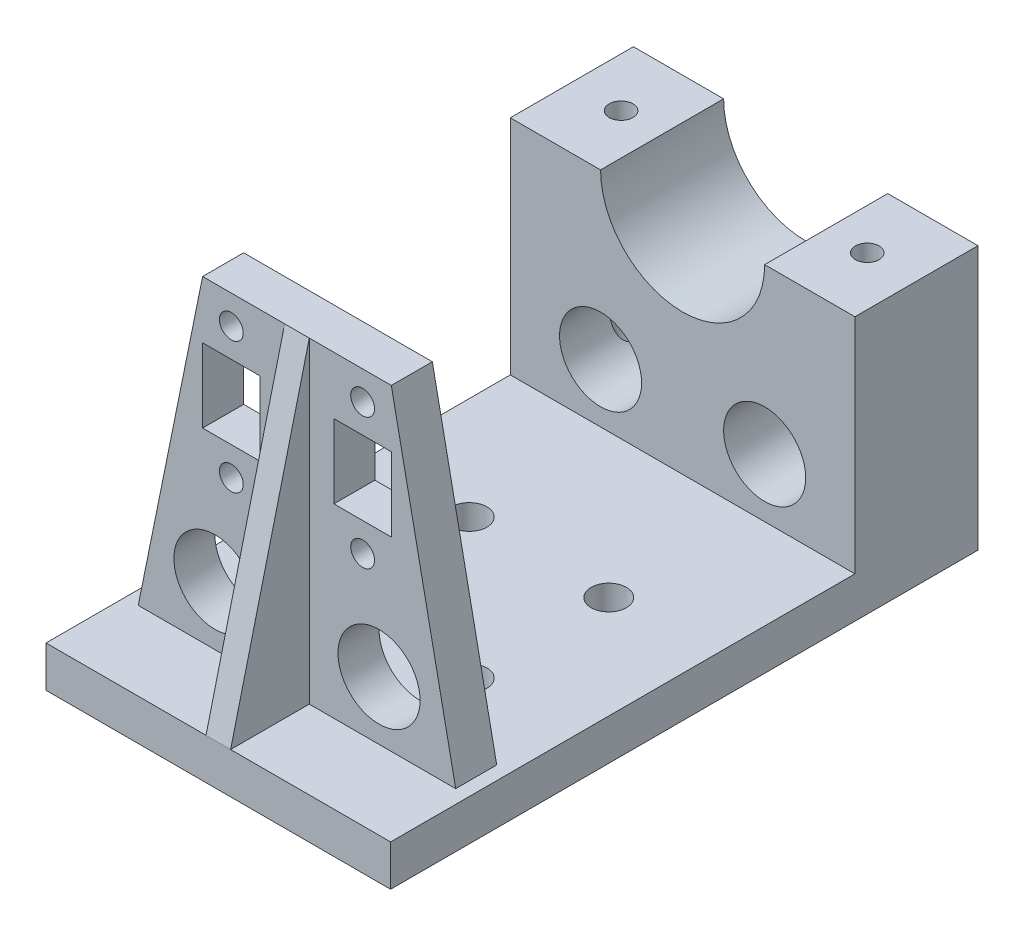
SolidWorks part; units mm, degrees
material "ABS"
ref_plane "Front Plane" through (0, 0, 0) normal (0, 0, 1) x (1, 0, 0)
ref_plane "Top Plane" through (0, 0, 0) normal (0, 1, 0) x (1, 0, 0)
ref_plane "Right Plane" through (0, 0, 0) normal (1, 0, 0) x (0, 0, -1)
sketch "Mouting Mount Sketch" plane through (0, 0, 0) normal (0, 0, 1) x (1, 0, 0)
  line L1 (25, -55) -> (-25, -55)
  line L2 (25, -55) -> (25, 0)
  line L3 (25, 0) -> (-25, 0)
  line L4 (-25, -55) -> (-25, 0)
  line L5 (25, -55) -> (-25, 0) construction
  line L6 (25, 0) -> (-25, -55) construction
  circle A0 centre (0, 0) radius 10
  point P3 (0, -27.5)
  dimension "D1" = 20
  dimension "D2" = 50
  dimension "D3" = 55
extrude "Motor Mount Solid" add sketch "Mouting Mount Sketch" along normal mid plane 15 contours A0 L3 L4 L1 L2 region at (0, -28.9088, 0)
sketch "Encoder Distance Sketch" plane through (0, -55, 0) normal (0, -1, 0) x (1, 0, 0)
  line L0 (25, 7.5) -> (25, -7.5) construction
  line L1 (-25, 7.5) -> (25, 7.5)
  line L2 (-25, 7.5) -> (-25, 49.5)
  line L3 (-25, 49.5) -> (25, 49.5)
  line L4 (25, 7.5) -> (25, 49.5)
  line L5 (-25, -7.5) -> (25, -7.5) construction
  line L6 (-25, -7.5) -> (-25, 54.5) construction
  line L7 (-25, 54.5) -> (25, 54.5) construction
  line L8 (25, -7.5) -> (25, 54.5) construction
  line M9 (-25, -7.5) -> (25, -7.5)
  line M10 (25, -7.5) -> (25, 7.5)
  line M11 (25, 7.5) -> (-25, 7.5)
  line M12 (-25, 7.5) -> (-25, -7.5)
  dimension "D1" = 42
  dimension "D2" = 5
extrude "Encoder Distance Solid" add sketch "Encoder Distance Sketch" along normal blind 5 contours M12 M9 M10 M11 | L4 L3 L2 M11 | L3 L8 L7 L6 region at (0, -55, 28.5) region at (0, -55, 0)
sketch "Encoder Mount Sketch" plane through (0, 0, 49.5) normal (0, 0, 1) x (1, 0, 0)
  line L0 (-25, -60) -> (-25, -55)
  line L1 (-8, -8) -> (8, -8) construction
  line L2 (-8, -8) -> (-8, 8) construction
  line L3 (-8, 8) -> (8, 8) construction
  line L4 (8, -8) -> (8, 8) construction
  line L5 (-8, -8) -> (8, 8) construction
  line L6 (-8, 8) -> (8, -8) construction
  line L7 (-11.5, -11.5) -> (11.5, -11.5) construction
  line L8 (-11.5, -11.5) -> (-11.5, 11.5) construction
  line L9 (-11.5, 11.5) -> (11.5, 11.5)
  line L10 (11.5, -11.5) -> (11.5, 11.5) construction
  line L11 (-11.5, -11.5) -> (11.5, 11.5) construction
  line L12 (-11.5, 11.5) -> (11.5, -11.5) construction
  line L13 (-11.5, 4.5) -> (-4.5, 4.5)
  line L14 (-11.5, 4.5) -> (-11.5, -4.5)
  line L15 (-11.5, -4.5) -> (-4.5, -4.5)
  line L16 (-4.5, 4.5) -> (-4.5, -4.5)
  line L17 (-11.5, 4.5) -> (-4.5, -4.5) construction
  line L18 (-11.5, -4.5) -> (-4.5, 4.5) construction
  line L19 (4.5, 4.5) -> (11.5, 4.5)
  line L20 (4.5, 4.5) -> (4.5, -4.5)
  line L21 (4.5, -4.5) -> (11.5, -4.5)
  line L22 (11.5, 4.5) -> (11.5, -4.5)
  line L23 (4.5, 4.5) -> (11.5, -4.5) construction
  line L24 (4.5, -4.5) -> (11.5, 4.5) construction
  line L25 (-25, -55) -> (-11.5, 11.5)
  line L26 (-25, -60) -> (25, -60)
  line L27 (25, -60) -> (25, -55)
  line L28 (25, -55) -> (11.5, 11.5)
  circle A0 centre (-8, 8) radius 1.45
  circle A1 centre (8, 8) radius 1.45
  circle A2 centre (-8, -8) radius 1.45
  circle A3 centre (8, -8) radius 1.45
  circle A4 centre (8, 8) radius 3.5 construction
  circle A5 centre (-8, 8) radius 3.5 construction
  circle A6 centre (-8, -8) radius 3.5 construction
  circle A7 centre (8, -8) radius 3.5 construction
  point P0 (0, 0)
  point P14 (0, 0)
  point P19 (-8, 0)
  point P24 (8, 0)
  dimension "D2" = 2.9
  dimension "D3" = 7
  dimension "D1" = 16
extrude "Encoder Mount Solid" add sketch "Encoder Mount Sketch" along normal blind 5
sketch "Motor Clamp Mounting Holes Sketch" plane through (0, 0, 0) normal (0, 1, 0) x (1, 0, 0)
  line L0 (-15, 0) -> (15, 0) construction
  circle A0 centre (-15, 0) radius 1.45
  circle A1 centre (15, 0) radius 1.45
  point P4 (0, 0)
  dimension "D2" = 2.9
  dimension "D1" = 30
extrude "Motor Clamp Mounting Holes Cut" cut sketch "Motor Clamp Mounting Holes Sketch" against normal through all both and the other way through all
sketch "Gusset Plate Sketch" plane through (0, 0, 54.5) normal (0, 0, 1) x (1, 0, 0)
  line L1 (-25, -55) -> (25, -55)
  line L2 (-25, -55) -> (-25, -60)
  line L3 (-25, -60) -> (25, -60)
  line L4 (25, -55) -> (25, -60)
extrude "Gusset Plate Solid" add sketch "Gusset Plate Sketch" along normal blind 16.5
sketch "Gusset Sketch" plane through (0, 0, 0) normal (1, 0, 0) x (0, 0, -1)
  line L0 (-54.5, 11.5) -> (-71, -55)
  line L1 (-71, -55) -> (-54.5, -55)
  line L2 (-54.5, -55) -> (-54.5, 11.5)
extrude "Gusset Solid" add sketch "Gusset Sketch" along normal mid plane 3
sketch "Mounting Plate Sketch" plane through (0, -55, 0) normal (0, 1, 0) x (1, 0, 0)
  line L0 (25, -7.5) -> (25, -49.5) construction
  line L1 (-25, -71) -> (25, -71)
  line L2 (-25, -71) -> (-25, 21)
  line L3 (-25, 21) -> (25, 21)
  line L4 (25, -71) -> (25, 21)
  line L5 (-19, -65) -> (19, -65) construction
  line L6 (-19, 15) -> (19, 15) construction
  circle A0 centre (-19, -65) radius 2.65
  circle A1 centre (19, -65) radius 6 construction
  circle A2 centre (19, -65) radius 2.65
  circle A3 centre (-19, -65) radius 6 construction
  circle A4 centre (-19, 15) radius 6 construction
  circle A5 centre (19, 15) radius 6 construction
  circle A6 centre (-19, 15) radius 2.65
  circle A7 centre (19, 15) radius 2.65
  point P10 (0, -65)
  point P18 (0, 15)
  dimension "D1" = 12
  dimension "D2" = 5.3
  dimension "D3" = 80
extrude "Mounting Plate Solid" add sketch "Mounting Plate Sketch" against normal up to surface (5 mm away) up to face at (-16.45, -60, 0)
sketch "Mounting Hole Sketch" plane through (0, -55, 0) normal (0, 1, 0) x (1, 0, 0)
  line L0 (25, 21) -> (25, -71) construction
  line L3 (25, -25) -> (-25, -25) construction
  line L4 (-25, -49.5) -> (-25, -7.5) construction
  circle A0 centre (-19, 15) radius 2.65
  circle A1 centre (19, 15) radius 2.65
  circle A3 centre (19, -65) radius 2.65
  circle A4 centre (-19, -65) radius 2.65
  circle A5 centre (-19, 15) radius 2.65 construction
extrude "Mounting Holes Cut" cut sketch "Mounting Hole Sketch" against normal through all both and the other way through all contours A3 | A4 | A1 | A0
sketch "Mounting Plate Trim Sketch" plane through (0, -55, 0) normal (0, 1, 0) x (1, 0, 0)
  line L1 (-25, 21) -> (25, 21)
  line L2 (-25, 21) -> (-25, 7.5)
  line L3 (-25, 7.5) -> (25, 7.5)
  line L4 (25, 21) -> (25, 7.5)
  line L5 (-25, -7.5) -> (25, -7.5)
  line L6 (-25, -7.5) -> (-25, -49.5)
  line L7 (-25, -49.5) -> (25, -49.5)
  line L8 (25, -7.5) -> (25, -49.5)
  line L9 (1.5, -54.5) -> (25, -54.5)
  line L10 (1.5, -54.5) -> (1.5, -71)
  line L11 (1.5, -71) -> (25, -71)
  line L12 (25, -54.5) -> (25, -71)
  line L13 (-1.5, -54.5) -> (-25, -54.5)
  line L14 (-1.5, -54.5) -> (-1.5, -71)
  line L15 (-1.5, -71) -> (-25, -71)
  line L16 (-25, -54.5) -> (-25, -71)
extrude "Mounting Plate Trim Cut" cut sketch "Mounting Plate Trim Sketch" against normal blind 2
sketch "Sketch2" plane through (0, 0, -7.5) normal (0, 0, -1) x (-1, 0, 0)
  line L1 (-21, -27.1363) -> (21, -27.1363)
  line L2 (-21, -27.1363) -> (-21, 27.1363)
  line L3 (-21, 27.1363) -> (21, 27.1363)
  line L4 (21, -27.1363) -> (21, 27.1363)
  line L5 (-21, -27.1363) -> (21, 27.1363) construction
  line L6 (-21, 27.1363) -> (21, -27.1363) construction
  line L7 (25, 60) -> (-25, 60)
  line L8 (25, 60) -> (25, -60)
  line L9 (25, -60) -> (-25, -60)
  line L10 (-25, 60) -> (-25, -60)
  line L11 (25, 60) -> (-25, -60) construction
  line L12 (25, -60) -> (-25, 60) construction
  point P0 (0, 0)
  point P7 (0, 0)
  dimension "D1" = 42
  dimension "D2" = 27.1363
extrude "Cut-Extrude1" cut sketch "Sketch2" against normal through all both and the other way through all
sketch "Sketch3" plane through (0, -27.1363, 0) normal (0, -1, 0) x (1, 0, 0)
  line L0 (21, 7.5) -> (21, -7.5) construction
  line L1 (-21, -7.5) -> (21, -7.5)
  line L2 (-21, -7.5) -> (-21, 64.0865)
  line L3 (-21, 64.0865) -> (21, 64.0865)
  line L4 (21, -7.5) -> (21, 64.0865)
  line L5 (-21, -7.5) -> (21, -7.5) construction
  line L6 (1.5, 64.0865) -> (-1.5, 64.0865) construction
extrude "Boss-Extrude1" add sketch "Sketch3" along normal blind 5
sketch "Sketch4" plane through (0, -27.1363, 0) normal (0, 1, 0) x (1, 0, 0)
  line L0 (21, -7.5) -> (21, -64.0865) construction
  line L1 (-21, -7.5) -> (21, -7.5) construction
  line L2 (-21, -7.5) -> (-21, -49.5) construction
  line L3 (-21, -49.5) -> (21, -49.5) construction
  line L4 (21, -7.5) -> (21, -49.5) construction
  line L5 (19.3435, -49.5) -> (-19.3435, -49.5) construction
  line L8 (-8.5, -42) -> (8.5, -42) construction
  line L9 (-8.5, -42) -> (-8.5, -25) construction
  line L10 (-8.5, -25) -> (8.5, -25) construction
  line L11 (8.5, -42) -> (8.5, -25) construction
  line L12 (-8.5, -42) -> (8.5, -25) construction
  line L13 (-8.5, -25) -> (8.5, -42) construction
  circle A0 centre (8.5, -25) radius 5 construction
  circle A1 centre (-8.5, -25) radius 5 construction
  circle A2 centre (-8.5, -42) radius 5 construction
  circle A3 centre (8.5, -42) radius 5 construction
  circle A4 centre (-8.5, -25) radius 2.15
  circle A5 centre (8.5, -25) radius 2.15
  circle A6 centre (-8.5, -42) radius 2.15
  circle A7 centre (8.5, -42) radius 2.15
  point P9 (0, -33.5)
  point P22 (0, 0)
  dimension "D1" = 10
  dimension "D4" = 4.3
  dimension "D2" = 17
  dimension "D3" = 17
  dimension "D5" = 16
extrude "Cut-Extrude2" cut sketch "Sketch4" against normal through all both and the other way through all
sketch "Sketch5" plane through (0, 0, 54.5) normal (0, 0, 1) x (1, 0, 0)
  line L0 (-10, -20) -> (10, -20) construction
  circle A0 centre (-10, -20) radius 5
  circle A1 centre (10, -20) radius 5
  point P3 (0, -20)
  point P5 (0, -18.4194)
  point P7 (0, -20)
  dimension "D1" = 10
  dimension "D2" = 20
  dimension "D3" = 20
extrude "Cut-Extrude3" cut sketch "Sketch5" against normal through all both
